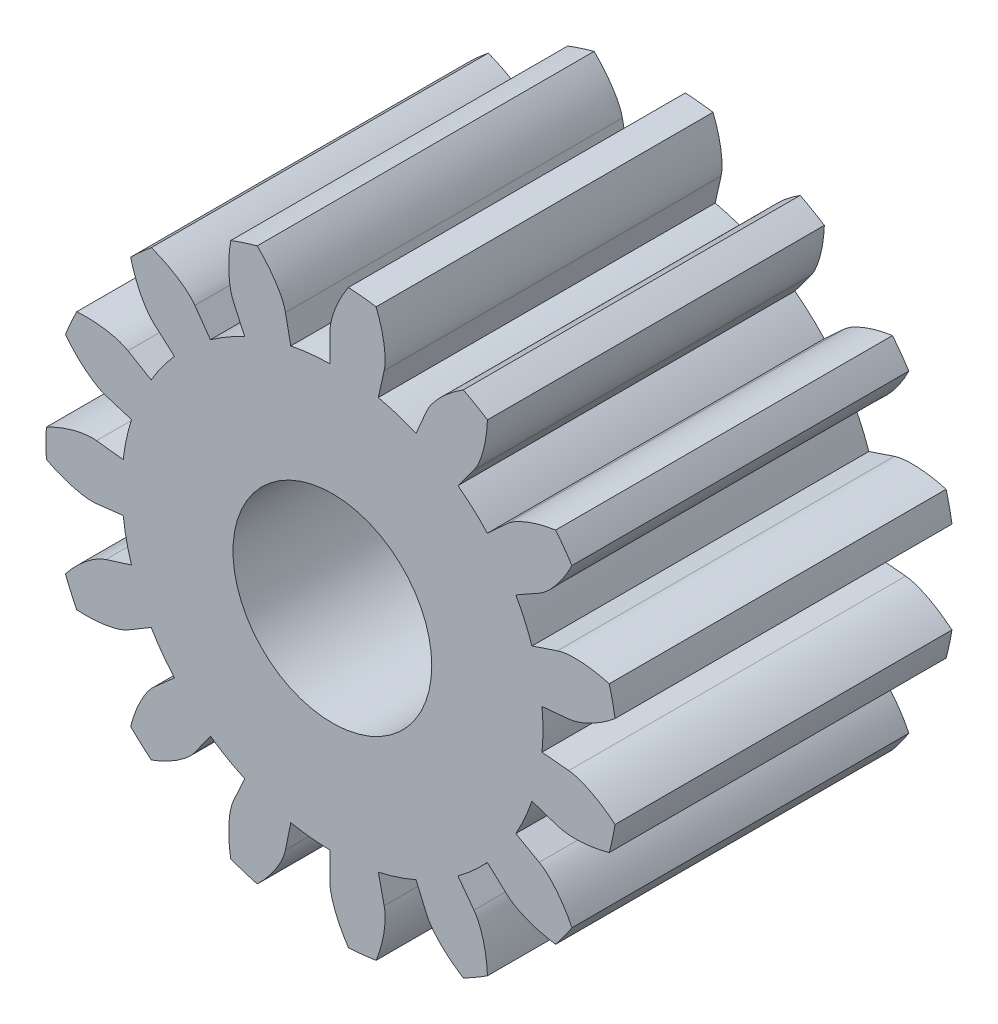
SolidWorks part; units mm, degrees
ref_plane "前视基准面" through (0, 0, 0) normal (0, 0, 1) x (1, 0, 0)
ref_plane "上视基准面" through (0, 0, 0) normal (0, 1, 0) x (1, 0, 0)
ref_plane "右视基准面" through (0, 0, 0) normal (1, 0, 0) x (0, 0, -1)
other "Configuration Table"
sketch "草图1" plane through (0, 0, 0) normal (0, 0, 1) x (1, 0, 0)
  line L0 (0, 0) -> (3.75, 0) construction
  line L1 (0, 0) -> (3.7295, 0.392) construction
  line L2 (0, 0) -> (3.5082, 0.3315)
  line L3 (3.7295, 0.392) -> (3.7295, -0.392) construction
  line L4 (0, 0) -> (3.5082, -0.3315)
  circle A0 centre (0, 0) radius 4.25
  circle A1 centre (0, 0) radius 3.75 construction
  circle A2 centre (0, 0) radius 3.125
  circle A3 centre (0, 0) radius 3.5238 construction
  circle A4 centre (0, 0) radius 1.475
  spline S0 degree 4 poles (3.5082, 0.3315) (3.535, 0.334) (3.6091, 0.3466) (3.7457, 0.3926) (3.9548, 0.4968) (4.2019, 0.6726) (4.484, 0.9409) (4.7638, 1.3017) (5.0111, 1.7378) (5.2598, 2.3657) (5.4025, 3.0275) (5.4503, 3.7286) (5.3927, 4.5628) (5.2285, 5.3841) (4.9003, 6.3007) (4.3829, 7.2502) (3.7346, 8.1151) (2.9759, 8.8843) (2.1253, 9.5502) (1.2008, 10.1079) (0.2174, 10.5546) (-0.6799, 10.8475) (-1.4694, 11.0287) (-2.0664, 11.1232) (-2.4714, 11.169) (-2.8005, 11.1962) (-3.0828, 11.2106) (-3.3043, 11.2186) (-3.5561, 11.2197) (-3.8112, 11.2172) (-4.0659, 11.2082) (-4.5131, 11.1822) (-4.8759, 11.139) (-5.2525, 11.0916) (-5.4338, 11.0564) (-5.5552, 11.0366) knots 0 0 0 0 0 0.005604 0.015718 0.02996 0.048734 0.068727 0.096889 0.125051 0.153212 0.209535 0.237696 0.271429 0.327752 0.384075 0.440398 0.496721 0.553044 0.609367 0.66569 0.722013 0.778336 0.806497 0.834659 0.84874 0.86282 0.876901 0.890982 0.900036 0.909091 0.931818 0.954545 0.977273 1 1 1 1 1 construction
  spline S1 degree 4 poles (3.5082, 0.3315) (3.535, 0.334) (3.6091, 0.3466) (3.7457, 0.3926) (3.9548, 0.4968) (4.2019, 0.6726) (4.484, 0.9409) (4.7638, 1.3017) (5.0111, 1.7378) (5.2598, 2.3657) (5.4025, 3.0275) (5.4503, 3.7286) (5.3927, 4.5628) (5.2285, 5.3841) (4.9003, 6.3007) (4.3829, 7.2502) (3.7346, 8.1151) (2.9759, 8.8843) (2.1253, 9.5502) (1.2008, 10.1079) (0.2174, 10.5546) (-0.6799, 10.8475) (-1.4694, 11.0287) (-2.0664, 11.1232) (-2.4714, 11.169) (-2.8005, 11.1962) (-3.0828, 11.2106) (-3.3043, 11.2186) (-3.5561, 11.2197) (-3.7056, 11.2183) (-3.7846, 11.2167) (-3.8239, 11.2156) knots 0 0 0 0 0 0.005604 0.015718 0.02996 0.048734 0.068727 0.096889 0.125051 0.153212 0.209535 0.237696 0.271429 0.327752 0.384075 0.440398 0.496721 0.553044 0.609367 0.66569 0.722013 0.778336 0.806497 0.834659 0.84874 0.86282 0.876901 0.890982 0.900036 0.909091 0.909091 0.909091 0.909091 0.909091
  spline S2 degree 4 poles (3.5082, -0.3315) (3.535, -0.334) (3.6091, -0.3466) (3.7457, -0.3926) (3.9548, -0.4968) (4.2019, -0.6726) (4.484, -0.9409) (4.7638, -1.3017) (5.0111, -1.7378) (5.2598, -2.3657) (5.4025, -3.0275) (5.4503, -3.7286) (5.3927, -4.5628) (5.2285, -5.3841) (4.9003, -6.3007) (4.3829, -7.2502) (3.7346, -8.1151) (2.9759, -8.8843) (2.1253, -9.5502) (1.2008, -10.1079) (0.2174, -10.5546) (-0.6799, -10.8475) (-1.4694, -11.0287) (-2.0664, -11.1232) (-2.4714, -11.169) (-2.8005, -11.1962) (-3.0828, -11.2106) (-3.3043, -11.2186) (-3.5561, -11.2197) (-3.8112, -11.2172) (-4.0659, -11.2082) (-4.5131, -11.1822) (-4.8759, -11.139) (-5.2525, -11.0916) (-5.4338, -11.0564) (-5.5552, -11.0366) knots 0 0 0 0 0 0.005604 0.015718 0.02996 0.048734 0.068727 0.096889 0.125051 0.153212 0.209535 0.237696 0.271429 0.327752 0.384075 0.440398 0.496721 0.553044 0.609367 0.66569 0.722013 0.778336 0.806497 0.834659 0.84874 0.86282 0.876901 0.890982 0.900036 0.909091 0.931818 0.954545 0.977273 1 1 1 1 1 construction
  spline S3 degree 4 poles (3.5082, -0.3315) (3.535, -0.334) (3.6091, -0.3466) (3.7457, -0.3926) (3.9548, -0.4968) (4.2019, -0.6726) (4.484, -0.9409) (4.7638, -1.3017) (5.0111, -1.7378) (5.2598, -2.3657) (5.4025, -3.0275) (5.4503, -3.7286) (5.3927, -4.5628) (5.2285, -5.3841) (4.9003, -6.3007) (4.3829, -7.2502) (3.7346, -8.1151) (2.9759, -8.8843) (2.1253, -9.5502) (1.2008, -10.1079) (0.2174, -10.5546) (-0.6799, -10.8475) (-1.4694, -11.0287) (-2.0664, -11.1232) (-2.4714, -11.169) (-2.8005, -11.1962) (-3.0828, -11.2106) (-3.3043, -11.2186) (-3.5561, -11.2197) (-3.7056, -11.2183) (-3.7846, -11.2167) (-3.8239, -11.2156) knots 0 0 0 0 0 0.005604 0.015718 0.02996 0.048734 0.068727 0.096889 0.125051 0.153212 0.209535 0.237696 0.271429 0.327752 0.384075 0.440398 0.496721 0.553044 0.609367 0.66569 0.722013 0.778336 0.806497 0.834659 0.84874 0.86282 0.876901 0.890982 0.900036 0.909091 0.909091 0.909091 0.909091 0.909091
  point P15 (3.7295, 0)
  dimension "齿顶圆直径" = 8.5
  dimension "分度圆直径" = 7.5
  dimension "齿根圆直径" = 6.25
  dimension "基圆直径" = 7.0477
  dimension "内孔直径" = 2.95
  dimension "渐近线镜像线夹角" = 6
extrude "凸台-拉伸1" add sketch "草图1" along normal blind 5 contours A0 | A4
extrude "切除-拉伸1" cut sketch "草图1<3>" along normal through all contours A2 S3 A0 S1 region at (3.7623, 0, 0)
sketch "草图1<3>" plane through (0, 0, 0) normal (0, 0, 1) x (1, 0, 0) same geometry as "草图1"
pattern_circular "阵列(圆周)1" count 15 every 24 about axis through (0, 0, 5) along (0, 0, 1) of "切除-拉伸1"
equation "\"m\"= 0.5'模数"
equation "\"z\"= 15'齿数"
equation "\"a\"= 20度'压力角"
equation "\"d\"= \"m\" * \"z\"'分度圆直径"
equation "\"da\"= ( \"z\" + 2 ) * \"m\"'齿顶圆直径"
equation "\"df\"= ( \"z\" - 2.5 ) * \"m\"'齿根圆直径"
equation "\"s\"= 0.5 * PI * \"m\"'分度圆齿厚"
equation "\"r\"= 0.38 * \"m\"'齿根圆角"
equation "\"B\"= 0.3 * \"d\"'齿厚"
equation "\"db\"= \"m\" * \"z\" * cos ( \"a\" )'基圆直径"
equation "\"rb\"= \"db\" / 2'基圆半径"
equation "\"齿顶圆直径@草图1\"= \"da\""
equation "\"分度圆直径@草图1\"= \"d\""
equation "\"齿根圆直径@草图1\"= \"df\""
equation "\"基圆直径@草图1\"= \"db\""
equation "\"渐近线镜像线夹角@草图1\"= 360 / 4 / \"z\""
equation "\"h\"= 5'齿轮厚度"
equation "\"ir\"= 2.95'内孔直径"
equation "\"内孔直径@草图1\"= \"ir\""
equation "\"齿轮厚@凸台-拉伸1\"= \"h\""
equation "\"齿轮夹角@阵列(圆周)1\"= 360 / \"z\""
equation "\"齿数@阵列(圆周)1\"= \"z\""
